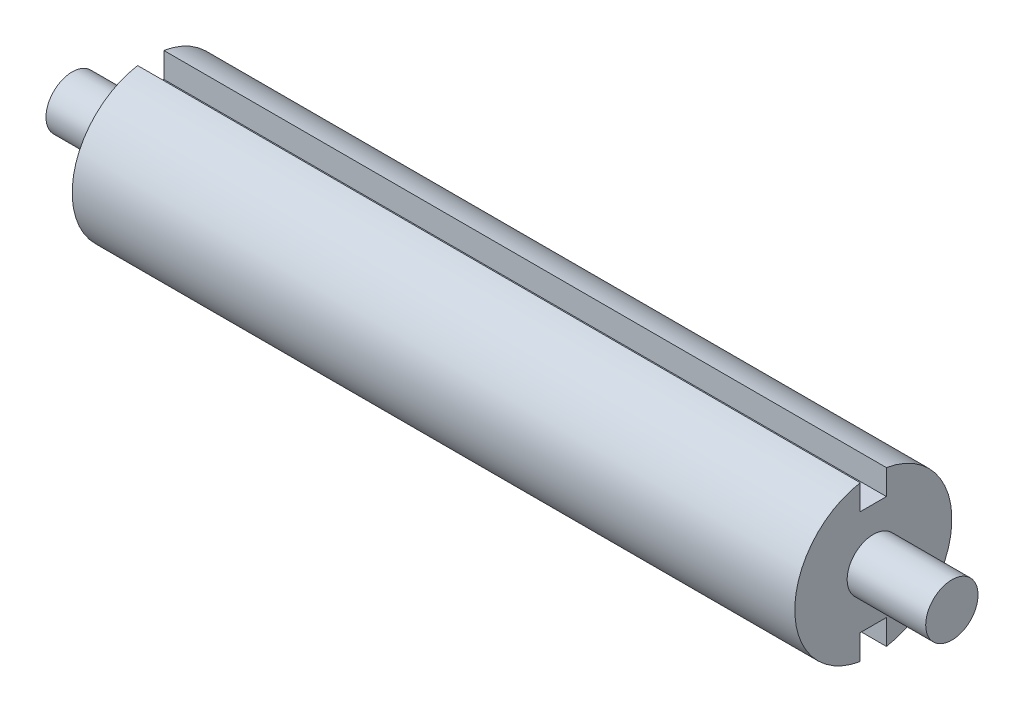
SolidWorks part; units mm, degrees
ref_plane "Front Plane" through (0, 0, 0) normal (0, 0, 1) x (1, 0, 0)
ref_plane "Top Plane" through (0, 0, 0) normal (0, 1, 0) x (1, 0, 0)
ref_plane "Right Plane" through (0, 0, 0) normal (1, 0, 0) x (0, 0, -1)
sketch "Sketch1" plane through (0, 0, 0) normal (0, 1, 0) x (1, 0, 0)
  line L0 (-106.68, 0) -> (106.68, 0)
  line L1 (-106.68, 0) -> (-106.68, 6.35)
  line L2 (-106.68, 6.35) -> (-87.63, 6.35)
  line L3 (-87.63, 6.35) -> (-87.63, 19.05)
  line L4 (-87.63, 19.05) -> (87.63, 19.05)
  line L5 (87.63, 19.05) -> (87.63, 6.35)
  line L6 (87.63, 6.35) -> (106.68, 6.35)
  line L7 (106.68, 6.35) -> (106.68, 0)
  point P10 (0, 0)
  dimension "D1" = 175.26
  dimension "D2" = 19.05
  dimension "D3" = 6.35
  dimension "D4" = 19.05
revolve "Revolve1" add sketch "Sketch1" angle 360 about L0
sketch "Sketch2" plane through (87.63, 0, 0) normal (1, 0, 0) x (0, 0, -1)
  line L0 (-6.35, 0) -> (6.35, 0) construction
  line L1 (-3.175, 12.7) -> (3.175, 12.7)
  line L2 (-3.175, 12.7) -> (-3.175, 19.05)
  line L3 (-3.175, 19.05) -> (3.175, 19.05)
  line L4 (3.175, 12.7) -> (3.175, 19.05)
  line L5 (-3.175, 12.7) -> (3.175, 19.05) construction
  line L6 (-3.175, 19.05) -> (3.175, 12.7) construction
  line L7 (-3.175, -19.05) -> (3.175, -12.7) construction
  line L8 (-3.175, -12.7) -> (3.175, -19.05) construction
  line L9 (3.175, -12.7) -> (3.175, -19.05)
  line L10 (-3.175, -19.05) -> (3.175, -19.05)
  line L11 (-3.175, -12.7) -> (-3.175, -19.05)
  line L12 (-3.175, -12.7) -> (3.175, -12.7)
  circle A0 centre (0, 0) radius 19.05 construction
  circle A1 centre (0, 0) radius 6.35 construction
  circle A2 centre (0, 0) radius 6.35 construction
  point P0 (0, 15.875)
  point P19 (0, -15.875)
  dimension "D1" = 6.35
  dimension "D2" = 6.35
extrude "Cut-Extrude1" cut sketch "Sketch2" against normal through all
